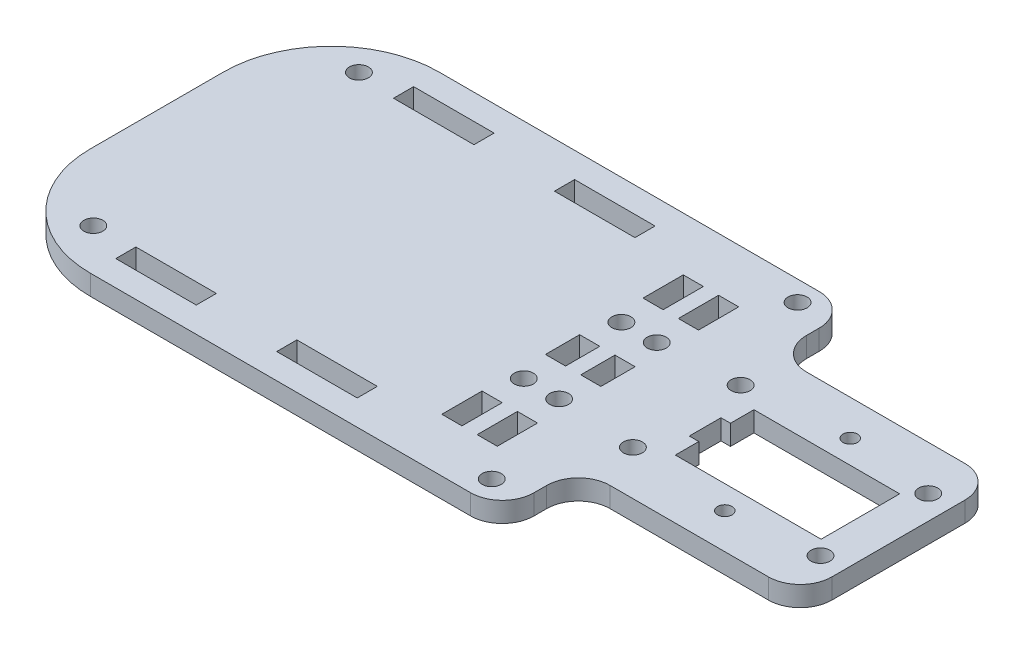
SolidWorks part; units mm, degrees
ref_plane "Front Plane" through (0, 0, 0) normal (0, 0, 1) x (1, 0, 0)
ref_plane "Top Plane" through (0, 0, 0) normal (0, 1, 0) x (1, 0, 0)
ref_plane "Right Plane" through (0, 0, 0) normal (1, 0, 0) x (0, 0, -1)
sketch "Sketch1" plane through (0, 0, 0) normal (0, 1, 0) x (1, 0, 0)
  line L0 (67.175, 40.2) -> (67.175, 14.8) construction
  line L1 (17, 0) -> (77, 0)
  line L2 (0, 17) -> (0, 38)
  line L3 (17, 55) -> (77, 55)
  line L4 (117, 17) -> (117, 38)
  line L5 (117, 27.5) -> (116.4302, 27.5) construction
  line L6 (64, 46.55) -> (67.175, 46.55)
  line L7 (64, 46.55) -> (64, 40.2)
  line L8 (64, 40.2) -> (67.175, 40.2)
  line L9 (67.175, 46.55) -> (67.175, 40.2)
  line L10 (64, 14.8) -> (67.175, 14.8)
  line L11 (64, 14.8) -> (64, 8.45)
  line L12 (64, 8.45) -> (67.175, 8.45)
  line L13 (67.175, 14.8) -> (67.175, 8.45)
  line L14 (67.175, 27.5) -> (47.2685, 27.5) construction
  line L15 (0, 27.5) -> (7.7524, 27.5) construction
  line L16 (65.5875, 40.2) -> (65.5875, 30.2) construction
  line L17 (67.175, 30.2) -> (64, 30.2)
  line L18 (67.175, 30.2) -> (67.175, 24.8)
  line L19 (67.175, 24.8) -> (64, 24.8)
  line L20 (64, 30.2) -> (64, 24.8)
  line L21 (65.5875, 24.8) -> (65.5875, 14.8) construction
  line L22 (69.575, 46.55) -> (72.75, 46.55)
  line L23 (69.575, 46.55) -> (69.575, 40.2)
  line L24 (69.575, 40.2) -> (72.75, 40.2)
  line L25 (72.75, 46.55) -> (72.75, 40.2)
  line L26 (69.575, 30.2) -> (72.75, 30.2)
  line L27 (69.575, 30.2) -> (69.575, 24.8)
  line L28 (69.575, 24.8) -> (72.75, 24.8)
  line L29 (72.75, 30.2) -> (72.75, 24.8)
  line L30 (69.575, 14.8) -> (72.75, 14.8)
  line L31 (69.575, 14.8) -> (69.575, 8.45)
  line L32 (69.575, 8.45) -> (72.75, 8.45)
  line L33 (72.75, 14.8) -> (72.75, 8.45)
  line L34 (71.1625, 40.2) -> (71.1625, 30.2) construction
  line L35 (71.1625, 24.8) -> (71.1625, 14.8) construction
  line L36 (64, 27.5) -> (67.175, 27.5) construction
  line L37 (72.75, 27.5) -> (69.575, 27.5) construction
  line L38 (55.1, 4) -> (55.1, 7.175)
  line L39 (17, 51) -> (29.7, 51)
  line L40 (17, 51) -> (17, 47.825)
  line L41 (17, 47.825) -> (29.7, 47.825)
  line L42 (29.7, 51) -> (29.7, 47.825)
  line L43 (42.4, 51) -> (55.1, 51)
  line L44 (42.4, 51) -> (42.4, 47.825)
  line L45 (42.4, 47.825) -> (55.1, 47.825)
  line L46 (55.1, 51) -> (55.1, 47.825)
  line L47 (42.4, 7.175) -> (55.1, 7.175)
  line L48 (42.4, 4) -> (42.4, 7.175)
  line L49 (42.4, 4) -> (55.1, 4)
  line L50 (29.7, 4) -> (29.7, 7.175)
  line L51 (17, 7.175) -> (29.7, 7.175)
  line L52 (17, 4) -> (17, 7.175)
  line L53 (17, 4) -> (29.7, 4)
  line L54 (88, 33.7) -> (111, 33.7)
  line L55 (88, 21.3) -> (111, 21.3)
  line L56 (111, 27.5) -> (86.5, 27.5) construction
  line L57 (86.5, 25) -> (88, 25)
  line L58 (88, 25) -> (88, 21.3)
  line L60 (82, 50) -> (82, 48)
  line L61 (87, 43) -> (112, 43)
  line L62 (87, 12) -> (112, 12)
  line L64 (111, 21.3) -> (111, 33.7)
  line L66 (82, 5) -> (82, 7)
  line L70 (88, 33.7) -> (88, 30)
  line L71 (88, 30) -> (86.5, 30)
  line L72 (86.5, 30) -> (86.5, 25)
  circle A0 centre (65.5875, 35.2) radius 1.5
  circle A1 centre (71.1625, 35.2) radius 1.5
  circle A2 centre (65.5875, 19.8) radius 1.5
  circle A3 centre (71.1625, 19.8) radius 1.5
  circle A4 centre (10.7398, 48.6273) radius 1.5
  circle A5 centre (10.7398, 6.7173) radius 1.5
  circle A6 centre (76.7798, 3.5423) radius 1.5
  circle A7 centre (76.7798, 51.8023) radius 1.5
  arc A8 (112, 43) -> (117, 38) centre (112, 38) cw
  circle A9 centre (83.6, 36) radius 1.5
  arc A10 (17, 0) -> (0, 17) centre (17, 17) cw
  arc A11 (0, 38) -> (17, 55) centre (17, 38) cw
  circle A12 centre (99.5, 37.4) radius 1.15
  circle A13 centre (99.5, 17.6) radius 1.15
  arc A14 (82, 48) -> (87, 43) centre (87, 48) ccw
  arc A15 (82, 50) -> (77, 55) centre (77, 50) ccw
  arc A16 (112, 12) -> (117, 17) centre (112, 17) ccw
  arc A17 (82, 7) -> (87, 12) centre (87, 7) cw
  arc A18 (82, 5) -> (77, 0) centre (77, 5) cw
  circle A19 centre (83.6, 19) radius 1.4999
  circle A20 centre (113.2, 19) radius 1.4999
  circle A21 centre (113.2, 36) radius 1.4999
  point P70 (10.7398, 48.6273)
  point P71 (10.7398, 6.7173)
  point P72 (76.7798, 51.8023)
  point P73 (76.7798, 3.5423)
  point P85 (117, 55)
  point P90 (0, 0)
  point P93 (0, 55)
  dimension "D19" = 3
  dimension "D20" = 3
  dimension "D21" = 3
  dimension "D22" = 3
  dimension "D34" = 3
  dimension "D35" = 3
  dimension "D36" = 3
  dimension "D37" = 3
  dimension "D38" = 12
  dimension "D39" = 2.3
  dimension "D43" = 5
  dimension "D44" = 17.5
  dimension "D1" = 117
  dimension "D2" = 0
  dimension "D3" = 55
  dimension "D4" = 3.175
  dimension "D5" = 3.175
  dimension "D6" = 6.35
  dimension "D7" = 6.35
  dimension "D8" = 38.1
  dimension "D9" = 17.5
  dimension "D10" = 64
  dimension "D11" = 5.4
  dimension "D12" = 5.4
  dimension "D13" = 2.4
  dimension "D14" = 2.4
  dimension "D15" = 2.4
  dimension "D16" = 3.175
  dimension "D17" = 3.175
  dimension "D18" = 3.175
  dimension "D23" = 0
  dimension "D24" = 0
  dimension "D25" = 12.7
  dimension "D26" = 12.7
  dimension "D27" = 12.7
  dimension "D28" = 17
  dimension "D29" = 4
  dimension "D30" = 4
  dimension "D31" = 3.175
  dimension "D32" = 3.175
  dimension "D33" = 6
  dimension "D40" = 9.9
  dimension "D41" = 11.5
  dimension "D42" = 35
  dimension "D45" = 15.9
  dimension "D46" = 15.9
  dimension "D47" = 8.5
  dimension "D48" = 8.5
  dimension "D49" = 8.5
  dimension "D50" = 8.5
  dimension "D51" = 13.7
  dimension "D52" = 13.7
  dimension "D53" = 12.4
  dimension "D54" = 6.2
  dimension "D55" = 23
  dimension "D56" = 23
  dimension "D57" = 24.5
extrude "Boss-Extrude1" add sketch "Sketch1" along normal blind 3.175
